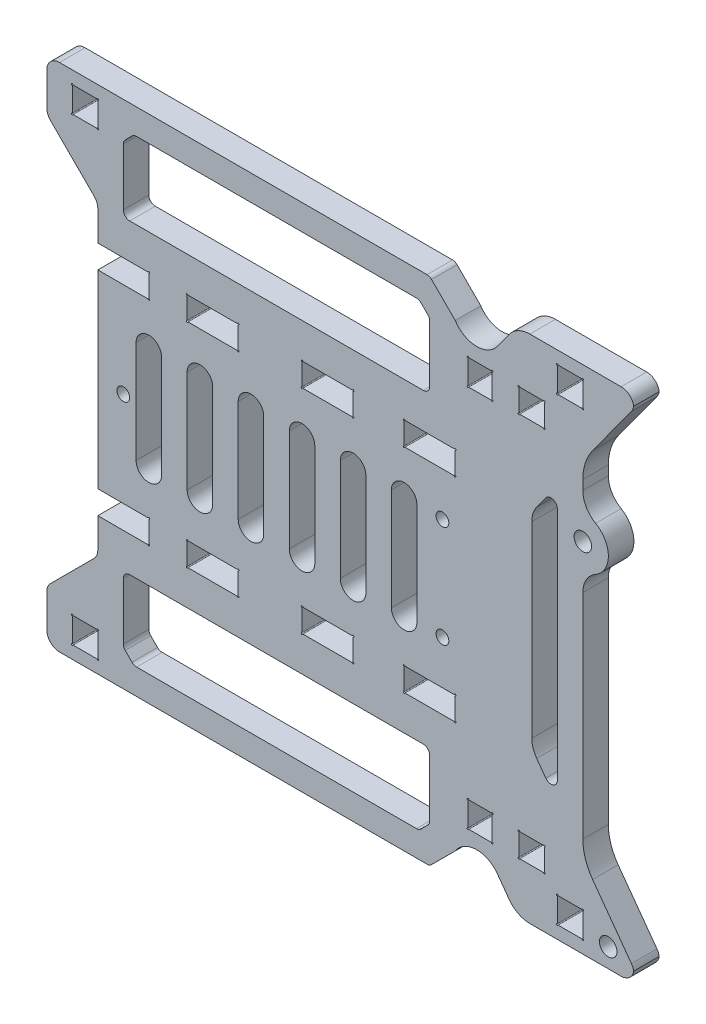
SolidWorks part; units mm, degrees
ref_plane "Front Plane" through (0, 0, 0) normal (0, 0, 1) x (1, 0, 0)
ref_plane "Top Plane" through (0, 0, 0) normal (0, 1, 0) x (1, 0, 0)
ref_plane "Right Plane" through (0, 0, 0) normal (1, 0, 0) x (0, 0, -1)
sketch "Sketch1" plane through (0, 0, 0) normal (0, 0, 1) x (1, 0, 0)
  line L0 (83.672, 0) -> (-43.8164, 0) construction
  line L1 (10.525, 38.1) -> (10.525, -38.1) construction
  line L2 (-27.575, 38.1) -> (48.625, 38.1)
  line L3 (99.425, -63.5) -> (99.425, -60.325)
  line L4 (99.425, -60.325) -> (74.025, -25.4)
  line L5 (-27.575, -63.5) -> (48.625, -63.5)
  line L6 (-27.575, 38.1) -> (-27.575, 54.5197)
  line L7 (48.625, 38.1) -> (48.625, 54.5197)
  line L8 (-24.9447, 57.15) -> (45.9947, 57.15)
  line L9 (-27.575, 63.5) -> (48.625, 63.5)
  line L10 (-33.925, 57.15) -> (-33.925, -57.15)
  line L11 (-27.575, 63.5) -> (-33.925, 57.15)
  line L12 (-24.9447, 57.15) -> (-27.575, 54.5197)
  line L13 (99.425, 63.5) -> (99.425, 60.325)
  line L14 (-23.0849, 59.0099) -> (-29.4349, 52.6599) construction
  line L15 (99.425, 60.325) -> (74.025, 25.4)
  line L16 (74.025, 25.4) -> (74.025, -25.4)
  line L17 (48.625, -38.1) -> (48.625, -54.5197)
  line L18 (-27.575, -38.1) -> (48.625, -38.1)
  line L19 (-24.9447, -57.15) -> (45.9947, -57.15)
  line L20 (-24.9447, -57.15) -> (-27.575, -54.5197)
  line L21 (-27.575, -38.1) -> (-27.575, -54.5197)
  line L22 (-27.575, -63.5) -> (-33.925, -57.15)
  line L23 (48.625, -63.5) -> (54.975, -57.15)
  line L24 (48.625, 63.5) -> (54.975, 57.15)
  line L25 (70.3271, -63.5) -> (99.425, -63.5)
  line L26 (45.9947, 57.15) -> (48.625, 54.5197)
  line L27 (45.9947, -57.15) -> (48.625, -54.5197)
  line L28 (70.3271, 63.5) -> (65.7089, 57.15)
  line L29 (70.3271, 63.5) -> (99.425, 63.5)
  line L30 (78.8831, 75.2646) -> (53.4831, 40.3396) construction
  line L31 (54.975, -42.3909) -> (54.975, -57.15)
  line L32 (70.3271, -63.5) -> (65.7089, -57.15)
  line L34 (48.625, -63.5) -> (54.975, -57.15)
  line L35 (65.7089, 57.15) -> (54.975, 42.3909)
  line L36 (54.975, 42.3909) -> (54.975, 57.15)
  line L37 (65.7089, -57.15) -> (54.975, -42.3909)
  point P7 (-27.575, 0)
  point P21 (74.025, 0)
  point P22 (-33.925, 0)
  dimension "D1" = 25.4
  dimension "D2" = 76.2
  dimension "D3" = 127
  dimension "D4" = 6.35
  dimension "D7" = 3.175
  dimension "D8" = 25.4
  dimension "D9" = 25.4
  dimension "D6" = 6.35
extrude "Boss-Extrude1" add sketch "Sketch1" along normal blind 6.35 contours L23 L32 L25 L3 L4 L16 L15 L13 L29 L28 L24 L9 L11 L10 L22 L5 L8 L26 L7 L2 L6 L12 L27 L19 L20 L21 L18 L17 region at (27.1557, 0, 0)
fillet "Fillet1" radius 6.35 4 edges at (70.3271, 63.5, 3.175) (70.3271, -63.5, 3.175) (54.975, -42.3909, 3.175) (54.975, 42.3909, 3.175)
fillet "Fillet3" radius 3.175 4 edges at (99.425, 63.5, 3.175) (99.425, 60.325, 3.175) (99.425, -60.325, 3.175) (99.425, -63.5, 3.175)
fillet "Fillet4" radius 6.35 2 edges at (74.025, -25.4, 3.175) (74.025, 25.4, 3.175)
fillet "Fillet7" radius 1.5875 4 edges at (-27.575, -38.1, 3.175) (48.625, -38.1, 3.175) (48.625, 38.1, 3.175) (-27.575, 38.1, 3.175)
fillet "Fillet8" radius 1.5875 2 edges at (48.625, -63.5, 3.175) (48.625, 63.5, 3.175)
fillet "Fillet9" radius 1.5875 8 edges at (-27.575, 54.5197, 3.175) (-24.9447, 57.15, 3.175) (-27.575, -54.5197, 3.175) (-24.9447, -57.15, 3.175) (45.9947, -57.15, 3.175) (48.625, -54.5197, 3.175) (48.625, 54.5197, 3.175) (45.9947, 57.15, 3.175)
sketch "Sketch2" plane through (0, 0, 6.35) normal (0, 0, 1) x (1, 0, 0)
  line L0 (-33.925, 0) -> (74.025, 0) construction
  line L1 (-33.925, 57.15) -> (-33.925, -57.15) construction
  line L2 (74.025, 23.3351) -> (74.025, -23.3351) construction
  line L3 (48.625, 39.6875) -> (48.625, 53.8622) construction
  line L4 (58.3484, 50.8) -> (63.9714, 50.8)
  line L5 (58.15, 50.6016) -> (58.15, 44.6484)
  line L6 (58.3484, 44.45) -> (63.9714, 44.45)
  line L7 (64.1698, 50.6016) -> (64.1698, 44.6484)
  line L8 (64.1698, -50.6016) -> (64.1698, -44.6484)
  line L9 (58.3484, -50.8) -> (63.9714, -50.8)
  line L10 (58.15, -50.6016) -> (58.15, -44.6484)
  line L11 (58.3484, -44.45) -> (63.9714, -44.45)
  arc A0 (58.3484, 50.8) -> (58.15, 50.6016) centre (58.15, 50.8) ccw
  arc A1 (64.1698, 50.6016) -> (63.9714, 50.8) centre (64.1698, 50.8) ccw
  arc A2 (63.9714, 44.45) -> (64.1698, 44.6484) centre (64.1698, 44.45) ccw
  arc A3 (58.15, 44.6484) -> (58.3484, 44.45) centre (58.15, 44.45) ccw
  arc A4 (63.9714, -44.45) -> (64.1698, -44.6484) centre (64.1698, -44.45) cw
  arc A5 (64.1698, -50.6016) -> (63.9714, -50.8) centre (64.1698, -50.8) cw
  arc A6 (58.3484, -50.8) -> (58.15, -50.6016) centre (58.15, -50.8) cw
  arc A7 (58.15, -44.6484) -> (58.3484, -44.45) centre (58.15, -44.45) cw
  point P10 (48.625, 46.7748)
  dimension "D5" = 0.3969
  dimension "D6" = 0.3969
  dimension "D7" = 0.3969
  dimension "D8" = 0.3969
  dimension "D1" = 6.0198
  dimension "D2" = 6.35
  dimension "D3" = 50.8
  dimension "D4" = 9.525
extrude "Cut-Extrude1" cut sketch "Sketch2" against normal through all
sketch "Sketch5" plane through (0, 0, 6.35) normal (0, 0, 1) x (1, 0, 0)
  line L0 (-33.925, 29.3675) -> (74.025, 29.3675) construction
  line L1 (-33.925, 57.15) -> (-33.925, -57.15) construction
  line L2 (74.025, 23.3351) -> (74.025, -23.3351) construction
  line L3 (-25.9875, 38.1) -> (47.0375, 38.1) construction
  line L4 (-33.925, 23.5763) -> (74.025, 23.5763) construction
  line L5 (-33.925, 0) -> (74.025, 0) construction
  line L6 (-11.5016, 29.3675) -> (0.8016, 29.3675)
  line L7 (-11.7, 29.169) -> (-11.7, 23.7747)
  line L8 (-11.5016, 23.5763) -> (0.8016, 23.5763)
  line L9 (1, 29.169) -> (1, 23.7747)
  line L10 (42.4734, 29.3675) -> (54.7766, 29.3675)
  line L11 (42.275, 29.169) -> (42.275, 23.7747)
  line L12 (42.4734, 23.5763) -> (54.7766, 23.5763)
  line L13 (54.975, 29.169) -> (54.975, 23.7747)
  line L14 (29.3766, 29.3675) -> (17.0734, 29.3675)
  line L15 (29.575, 29.169) -> (29.575, 23.7747)
  line L16 (29.3766, 23.5763) -> (17.0734, 23.5763)
  line L17 (16.875, 29.169) -> (16.875, 23.7747)
  line L18 (-21.4234, 29.3675) -> (-33.925, 29.3675)
  line L19 (-21.225, 29.169) -> (-21.225, 23.7747)
  line L20 (-21.4234, 23.5763) -> (-33.925, 23.5763)
  line L21 (-33.925, 29.3675) -> (-33.925, 23.5763)
  line L22 (-33.925, -29.3675) -> (-33.925, -23.5763)
  line L23 (-21.4234, -23.5763) -> (-33.925, -23.5763)
  line L24 (-21.225, -29.169) -> (-21.225, -23.7747)
  line L25 (-21.4234, -29.3675) -> (-33.925, -29.3675)
  line L26 (16.875, -29.169) -> (16.875, -23.7747)
  line L27 (29.3766, -23.5763) -> (17.0734, -23.5763)
  line L28 (29.575, -29.169) -> (29.575, -23.7747)
  line L29 (29.3766, -29.3675) -> (17.0734, -29.3675)
  line L30 (54.975, -29.169) -> (54.975, -23.7747)
  line L31 (42.4734, -23.5763) -> (54.7766, -23.5763)
  line L32 (42.275, -29.169) -> (42.275, -23.7747)
  line L33 (42.4734, -29.3675) -> (54.7766, -29.3675)
  line L34 (1, -29.169) -> (1, -23.7747)
  line L35 (-11.5016, -23.5763) -> (0.8016, -23.5763)
  line L36 (-11.7, -29.169) -> (-11.7, -23.7747)
  line L37 (-11.5016, -29.3675) -> (0.8016, -29.3675)
  line L38 (-33.925, 26.4719) -> (54.975, 26.4719) construction
  arc A0 (-21.225, 29.169) -> (-21.4234, 29.3675) centre (-21.225, 29.3675) ccw
  arc A1 (-11.5016, 29.3675) -> (-11.7, 29.169) centre (-11.7, 29.3675) ccw
  arc A2 (1, 29.169) -> (0.8016, 29.3675) centre (1, 29.3675) ccw
  arc A3 (29.575, 29.169) -> (29.3766, 29.3675) centre (29.575, 29.3675) ccw
  arc A4 (17.0734, 29.3675) -> (16.875, 29.169) centre (16.875, 29.3675) ccw
  arc A5 (54.975, 29.169) -> (54.7766, 29.3675) centre (54.975, 29.3675) ccw
  arc A6 (42.4734, 29.3675) -> (42.275, 29.169) centre (42.275, 29.3675) ccw
  arc A7 (17.0734, 23.5763) -> (16.875, 23.7747) centre (16.875, 23.5763) cw
  arc A8 (29.575, 23.7747) -> (29.3766, 23.5763) centre (29.575, 23.5763) cw
  arc A9 (42.4734, 23.5763) -> (42.275, 23.7747) centre (42.275, 23.5763) cw
  arc A10 (54.975, 23.7747) -> (54.7766, 23.5763) centre (54.975, 23.5763) cw
  arc A11 (1, 23.7747) -> (0.8016, 23.5763) centre (1, 23.5763) cw
  arc A12 (-11.5016, 23.5763) -> (-11.7, 23.7747) centre (-11.7, 23.5763) cw
  arc A13 (-21.225, 23.7747) -> (-21.4234, 23.5763) centre (-21.225, 23.5763) cw
  arc A14 (-21.225, -23.7747) -> (-21.4234, -23.5763) centre (-21.225, -23.5763) ccw
  arc A15 (-11.5016, -23.5763) -> (-11.7, -23.7747) centre (-11.7, -23.5763) ccw
  arc A16 (1, -23.7747) -> (0.8016, -23.5763) centre (1, -23.5763) ccw
  arc A17 (54.975, -23.7747) -> (54.7766, -23.5763) centre (54.975, -23.5763) ccw
  arc A18 (42.4734, -23.5763) -> (42.275, -23.7747) centre (42.275, -23.5763) ccw
  arc A19 (29.575, -23.7747) -> (29.3766, -23.5763) centre (29.575, -23.5763) ccw
  arc A20 (17.0734, -23.5763) -> (16.875, -23.7747) centre (16.875, -23.5763) ccw
  arc A21 (42.4734, -29.3675) -> (42.275, -29.169) centre (42.275, -29.3675) cw
  arc A22 (54.975, -29.169) -> (54.7766, -29.3675) centre (54.975, -29.3675) cw
  arc A23 (17.0734, -29.3675) -> (16.875, -29.169) centre (16.875, -29.3675) cw
  arc A24 (29.575, -29.169) -> (29.3766, -29.3675) centre (29.575, -29.3675) cw
  arc A25 (1, -29.169) -> (0.8016, -29.3675) centre (1, -29.3675) cw
  arc A26 (-11.5016, -29.3675) -> (-11.7, -29.169) centre (-11.7, -29.3675) cw
  arc A27 (-21.225, -29.169) -> (-21.4234, -29.3675) centre (-21.225, -29.3675) cw
  dimension "D11" = 0.3969
  dimension "D12" = 0.3969
  dimension "D13" = 0.3969
  dimension "D14" = 0.3969
  dimension "D15" = 0.3969
  dimension "D16" = 0.3969
  dimension "D17" = 0.3969
  dimension "D1" = 8.7325
  dimension "D3" = 12.7
  dimension "D4" = 12.7
  dimension "D5" = 41.275
  dimension "D6" = 34.925
  dimension "D7" = 12.7
  dimension "D8" = 12.7
  dimension "D9" = 50.8
  dimension "D10" = 0
  dimension "D2" = 5.7912
extrude "Cut-Extrude4" cut sketch "Sketch5" against normal through all
sketch "Sketch6" plane through (0, 0, 6.35) normal (0, 0, 1) x (1, 0, 0)
  line L0 (80.375, 34.1312) -> (80.375, -34.1312)
  line L1 (98.8177, 59.49) -> (75.2395, 27.07) construction
  line L2 (98.8177, -59.49) -> (75.2395, -27.07) construction
  line L3 (74.025, 23.3351) -> (74.025, -23.3351) construction
  line L4 (86.725, 34.1312) -> (86.725, -34.1312)
  line L5 (86.725, 34.1312) -> (86.725, 42.8625)
  line L6 (86.725, 42.8625) -> (80.375, 34.1312)
  line L7 (86.725, -34.1312) -> (86.725, -42.8625)
  line L8 (86.725, -42.8625) -> (80.375, -34.1312)
  dimension "D1" = 6.35
  dimension "D2" = 6.35
extrude "Boss-Extrude2" add sketch "Sketch6" against normal blind 6.35
fillet "Fillet10" radius 1.5875 2 edges at (80.375, -34.1312, 3.175) (80.375, 34.1312, 3.175)
fillet "Fillet11" radius 12.7 2 edges at (86.725, 42.8625, 3.175) (86.725, -42.8625, 3.175)
hole_wizard "11/64 (0.17188) Diameter Hole1" positions "Sketch8" profile "Sketch7" hole size "11/64" standard "ANSI Inch" end condition through all
sketch "Sketch8" plane through (0, 0, 6.35) normal (0, 0, 1) x (1, 0, 0)
  line L1 (-33.925, -29.3675) -> (-33.925, -57.15) construction
  line L2 (73.5606, 63.5) -> (96.25, 63.5) construction
  point P0 (86.725, 25.4)
  dimension "D1" = 38.1
  dimension "D2" = 120.65
sketch "Sketch7" plane through (86.725, 25.4, 6.35) normal (1, 0, 0) x (0, -1, 0)
  line L0 (0, 0) -> (0, 6.35)
  line L1 (0, 6.35) -> (2.1829, 6.35)
  line L2 (2.1829, 6.35) -> (2.1829, 0)
  line L5 (2.1829, 0) -> (0, 0)
  line L11 (0, -6.35) -> (0, 107.95) construction
  dimension "Thru Hole Dia." = 4.3658
  dimension "Thru Hole Depth" = 6.35
sketch "Sketch10" plane through (0, 0, 6.35) normal (0, 0, 1) x (1, 0, 0)
  line L0 (51.8, 63.5) -> (51.8, -63.5) construction
  line L1 (-27.575, 63.5) -> (47.9674, 63.5) construction
  line L2 (-27.575, -63.5) -> (47.9674, -63.5) construction
  line L3 (23.225, 29.3675) -> (23.225, -29.3675) construction
  line L4 (29.3766, 29.3675) -> (17.0734, 29.3675) construction
  line L5 (17.0734, -29.3675) -> (29.3766, -29.3675) construction
  line L6 (-27.575, 63.5) -> (-27.575, -63.5) construction
  line L7 (-33.925, 0) -> (74.025, 0) construction
  line L8 (-33.925, 23.5763) -> (-33.925, -23.5763) construction
  line L9 (74.025, 23.3351) -> (74.025, -23.3351) construction
  circle A0 centre (51.8, 12.7) radius 1.5875
  circle A1 centre (51.8, -12.7) radius 1.5875
  circle A2 centre (-27.575, 0) radius 1.5875
  dimension "D3" = 3.175
  dimension "D5" = 79.375
  dimension "D1" = 28.575
  dimension "D2" = 79.375
  dimension "D4" = 12.7
extrude "Cut-Extrude6" cut sketch "Sketch10" against normal through all
sketch "Sketch11" plane through (0, 0, 6.35) normal (0, 0, 1) x (1, 0, 0)
  line L0 (-62.0481, -60.325) -> (124.8486, -60.325) construction
  line L1 (-27.575, -63.5) -> (47.9674, -63.5) construction
  line L2 (-27.575, -63.5) -> (-33.925, -57.15)
  line L3 (-33.925, -57.15) -> (-33.925, -50.8)
  line L4 (-33.925, -50.8) -> (-33.925, -38.1)
  line L5 (-46.625, -50.8) -> (-46.625, -63.5)
  line L6 (-46.625, -63.5) -> (-27.575, -63.5)
  line L7 (-46.625, -50.8) -> (-33.925, -38.1)
  line L8 (-33.925, -29.3675) -> (-33.925, -57.15) construction
  line L9 (-46.625, 63.5) -> (-27.575, 63.5)
  line L10 (-33.925, 0) -> (74.025, 0) construction
  line L11 (-46.625, 50.8) -> (-46.625, 63.5)
  line L12 (-33.925, 23.5763) -> (-33.925, -23.5763) construction
  line L13 (74.025, 23.3351) -> (74.025, -23.3351) construction
  line L14 (-46.625, 50.8) -> (-33.925, 38.1)
  line L15 (-33.925, 57.15) -> (-33.925, 50.8)
  line L16 (-27.575, 63.5) -> (-33.925, 57.15)
  line L17 (-33.925, 50.8) -> (-33.925, 38.1)
  point P2 (10.1962, -63.5)
  dimension "D1" = 3.175
  dimension "D2" = 12.7
  dimension "D3" = 12.7
extrude "Boss-Extrude4" add sketch "Sketch11" against normal blind 6.35
sketch "Sketch12" plane through (0, 0, 6.35) normal (0, 0, 1) x (1, 0, 0)
  line L0 (73.5606, -63.5) -> (96.25, -63.5) construction
  line L1 (86.5266, -60.325) -> (80.5734, -60.325)
  line L2 (86.725, -60.1266) -> (86.725, -54.1734)
  line L3 (86.5266, -53.975) -> (80.5734, -53.975)
  line L4 (80.375, -60.1266) -> (80.375, -54.1734)
  line L5 (-33.925, -29.3675) -> (-33.925, -38.1) construction
  line L6 (-33.925, 0) -> (74.025, 0) construction
  line L7 (86.725, 60.1266) -> (86.725, 54.1734)
  line L8 (86.5266, 60.325) -> (80.5734, 60.325)
  line L9 (80.375, 60.1266) -> (80.375, 54.1734)
  line L10 (86.5266, 53.975) -> (80.5734, 53.975)
  line L11 (83.55, -60.325) -> (-33.7266, -60.325) construction
  line L12 (-34.1234, -60.325) -> (-54.5439, -60.325) construction
  line L13 (-34.1234, -60.325) -> (-40.0766, -60.325)
  line L14 (-33.925, -60.1266) -> (-33.925, -54.1734)
  line L15 (-34.1234, -53.975) -> (-40.0766, -53.975)
  line L16 (-40.275, -60.1266) -> (-40.275, -54.1734)
  line L17 (-34.1234, 60.325) -> (-40.0766, 60.325)
  line L18 (-33.925, 60.1266) -> (-33.925, 54.1734)
  line L19 (-40.275, 60.1266) -> (-40.275, 54.1734)
  line L20 (-34.1234, 53.975) -> (-40.0766, 53.975)
  arc A0 (-40.275, 60.1266) -> (-40.0766, 60.325) centre (-40.275, 60.325) cw
  arc A1 (80.5734, -53.975) -> (80.375, -54.1734) centre (80.375, -53.975) ccw
  arc A2 (86.725, -54.1734) -> (86.5266, -53.975) centre (86.725, -53.975) ccw
  arc A3 (80.375, -60.1266) -> (80.5734, -60.325) centre (80.375, -60.325) ccw
  arc A4 (86.5266, -60.325) -> (86.725, -60.1266) centre (86.725, -60.325) ccw
  arc A5 (86.5266, 60.325) -> (86.725, 60.1266) centre (86.725, 60.325) cw
  arc A6 (80.375, 60.1266) -> (80.5734, 60.325) centre (80.375, 60.325) cw
  arc A7 (80.5734, 53.975) -> (80.375, 54.1734) centre (80.375, 53.975) cw
  arc A8 (86.725, 54.1734) -> (86.5266, 53.975) centre (86.725, 53.975) cw
  arc A9 (-40.0766, -53.975) -> (-40.275, -54.1734) centre (-40.275, -53.975) ccw
  arc A10 (-33.925, -54.1734) -> (-34.1234, -53.975) centre (-33.925, -53.975) ccw
  arc A11 (-34.1234, -60.325) -> (-33.925, -60.1266) centre (-33.925, -60.325) ccw
  arc A12 (-40.275, -60.1266) -> (-40.0766, -60.325) centre (-40.275, -60.325) ccw
  arc A13 (-34.1234, 60.325) -> (-33.925, 60.1266) centre (-33.925, 60.325) cw
  arc A14 (-33.925, 54.1734) -> (-34.1234, 53.975) centre (-33.925, 53.975) cw
  arc A15 (-40.0766, 53.975) -> (-40.275, 54.1734) centre (-40.275, 53.975) cw
  point P4 (84.9053, -63.5)
  dimension "D5" = 0.3969
  dimension "D6" = 0.3969
  dimension "D7" = 0.3969
  dimension "D8" = 0.3969
  dimension "D12" = 0.3969
  dimension "D13" = 0.3969
  dimension "D14" = 0.3969
  dimension "D15" = 0.3969
  dimension "D1" = 6.35
  dimension "D2" = 6.35
  dimension "D3" = 3.175
  dimension "D4" = 114.3
  dimension "D9" = 6.35
  dimension "D10" = 6.35
  dimension "D11" = 120.65
extrude "Cut-Extrude7" cut sketch "Sketch12" against normal blind 6.35
fillet "Fillet12" radius 3.175 6 edges at (-46.625, 63.5, 3.175) (-46.625, 50.8, 3.175) (-33.925, 38.1, 3.175) (-46.625, -63.5, 3.175) (-46.625, -50.8, 3.175) (-33.925, -38.1, 3.175)
hole_wizard "11/64 (0.17188) Diameter Hole2" positions "Sketch14" profile "Sketch13" hole size "11/64" standard "ANSI Inch" end condition through all
sketch "Sketch14" plane through (0, 0, 0) normal (0, 0, -1) x (-1, 0, 0)
  line L0 (-73.5606, -63.5) -> (-96.25, -63.5) construction
  point P0 (-93.0328, -58.7375)
  dimension "D1" = 4.7625
  dimension "D2" = 6.35
sketch "Sketch13" plane through (93.0328, -58.7375, 0) normal (1, 0, 0) x (0, 1, 0)
  line L0 (0, 0) -> (0, 6.35)
  line L1 (0, 6.35) -> (2.1829, 6.35)
  line L2 (2.1829, 6.35) -> (2.1829, 0)
  line L5 (2.1829, 0) -> (0, 0)
  line L11 (0, -6.35) -> (0, 107.95) construction
  dimension "Thru Hole Dia." = 4.3658
  dimension "Thru Hole Depth" = 6.35
sketch "Sketch15" plane through (0, 0, 6.35) normal (0, 0, 1) x (1, 0, 0)
  line L0 (-33.925, 0) -> (45.45, 0) construction
  line L1 (-33.925, 23.5763) -> (-33.925, -23.5763) construction
  line L3 (-21.225, -12.7) -> (-21.225, 12.7) construction
  line L4 (-24.4, -12.7) -> (-24.4, 12.7)
  line L5 (-18.05, -12.7) -> (-18.05, 12.7)
  line L6 (-8.525, -12.7) -> (-8.525, 12.7) construction
  line L7 (-11.7, -12.7) -> (-11.7, 12.7)
  line L8 (-5.35, -12.7) -> (-5.35, 12.7)
  line L9 (4.175, -12.7) -> (4.175, 12.7) construction
  line L10 (1, -12.7) -> (1, 12.7)
  line L11 (7.35, -12.7) -> (7.35, 12.7)
  line L12 (16.875, -12.7) -> (16.875, 12.7) construction
  line L13 (13.7, -12.7) -> (13.7, 12.7)
  line L14 (20.05, -12.7) -> (20.05, 12.7)
  line L15 (29.575, -12.7) -> (29.575, 12.7) construction
  line L16 (26.4, -12.7) -> (26.4, 12.7)
  line L17 (32.75, -12.7) -> (32.75, 12.7)
  line L18 (42.275, -12.7) -> (42.275, 12.7) construction
  line L19 (39.1, -12.7) -> (39.1, 12.7)
  line L20 (45.45, -12.7) -> (45.45, 12.7)
  arc A0 (-24.4, -12.7) -> (-18.05, -12.7) centre (-21.225, -12.7) ccw
  arc A1 (-18.05, 12.7) -> (-24.4, 12.7) centre (-21.225, 12.7) ccw
  arc A2 (-11.7, -12.7) -> (-5.35, -12.7) centre (-8.525, -12.7) ccw
  arc A3 (-5.35, 12.7) -> (-11.7, 12.7) centre (-8.525, 12.7) ccw
  arc A4 (1, -12.7) -> (7.35, -12.7) centre (4.175, -12.7) ccw
  arc A5 (7.35, 12.7) -> (1, 12.7) centre (4.175, 12.7) ccw
  arc A6 (13.7, -12.7) -> (20.05, -12.7) centre (16.875, -12.7) ccw
  arc A7 (20.05, 12.7) -> (13.7, 12.7) centre (16.875, 12.7) ccw
  arc A8 (26.4, -12.7) -> (32.75, -12.7) centre (29.575, -12.7) ccw
  arc A9 (32.75, 12.7) -> (26.4, 12.7) centre (29.575, 12.7) ccw
  arc A10 (39.1, -12.7) -> (45.45, -12.7) centre (42.275, -12.7) ccw
  arc A11 (45.45, 12.7) -> (39.1, 12.7) centre (42.275, 12.7) ccw
  point P8 (-21.225, 0)
  point P17 (-8.525, 0)
  point P24 (4.175, 0)
  point P31 (16.875, 0)
  point P38 (29.575, 0)
  point P43 (42.275, 0)
  dimension "D1" = 12.7
  dimension "D2" = 6
extrude "Cut-Extrude8" cut sketch "Sketch15" against normal through all
sketch "Sketch16" plane through (0, 0, 6.35) normal (0, 0, 1) x (1, 0, 0)
  line L0 (73.5606, 63.5) -> (96.25, 63.5) construction
  line L1 (76.9593, 50.8) -> (71.0062, 50.8)
  line L2 (77.1578, 50.6016) -> (77.1578, 45.1564)
  line L3 (76.9593, 44.958) -> (71.0062, 44.958)
  line L4 (70.8078, 50.6016) -> (70.8078, 45.1564)
  line L8 (70.8078, -50.6016) -> (70.8078, -45.1564)
  line L9 (76.9593, -44.958) -> (71.0062, -44.958)
  line L10 (77.1578, -50.6016) -> (77.1578, -45.1564)
  line L11 (76.9593, -50.8) -> (71.0062, -50.8)
  arc A0 (71.0062, 50.8) -> (70.8078, 50.6016) centre (70.8078, 50.8) ccw
  arc A1 (77.1578, 50.6016) -> (76.9593, 50.8) centre (77.1578, 50.8) ccw
  arc A2 (76.9593, 44.958) -> (77.1578, 45.1564) centre (77.1578, 44.958) ccw
  arc A3 (70.8078, 45.1564) -> (71.0062, 44.958) centre (70.8078, 44.958) ccw
  arc A4 (70.8078, -45.1564) -> (71.0062, -44.958) centre (70.8078, -44.958) cw
  arc A5 (76.9593, -44.958) -> (77.1578, -45.1564) centre (77.1578, -44.958) cw
  arc A6 (77.1578, -50.6016) -> (76.9593, -50.8) centre (77.1578, -50.8) cw
  arc A7 (71.0062, -50.8) -> (70.8078, -50.6016) centre (70.8078, -50.8) cw
  dimension "D5" = 0.3969
  dimension "D6" = 0.3969
  dimension "D7" = 0.3969
  dimension "D8" = 0.3969
  dimension "D1" = 6.35
  dimension "D2" = 5.842
  dimension "D3" = 22.225
  dimension "D4" = 12.7
extrude "Cut-Extrude9" cut sketch "Sketch16" against normal through all
sketch "Sketch17" plane through (0, 0, 6.35) normal (0, 0, 1) x (1, 0, 0)
  circle A0 centre (86.725, 25.4) radius 6.35
  circle A1 centre (86.725, 25.4) radius 2.1829
extrude "Boss-Extrude5" add sketch "Sketch17" against normal up to surface (6.35 mm away) up to face at (73.9828, -47.879, 0)
fillet "Fillet13" radius 6.35 2 edges at (86.725, 19.05, 3.175) (86.725, 31.75, 3.175)
